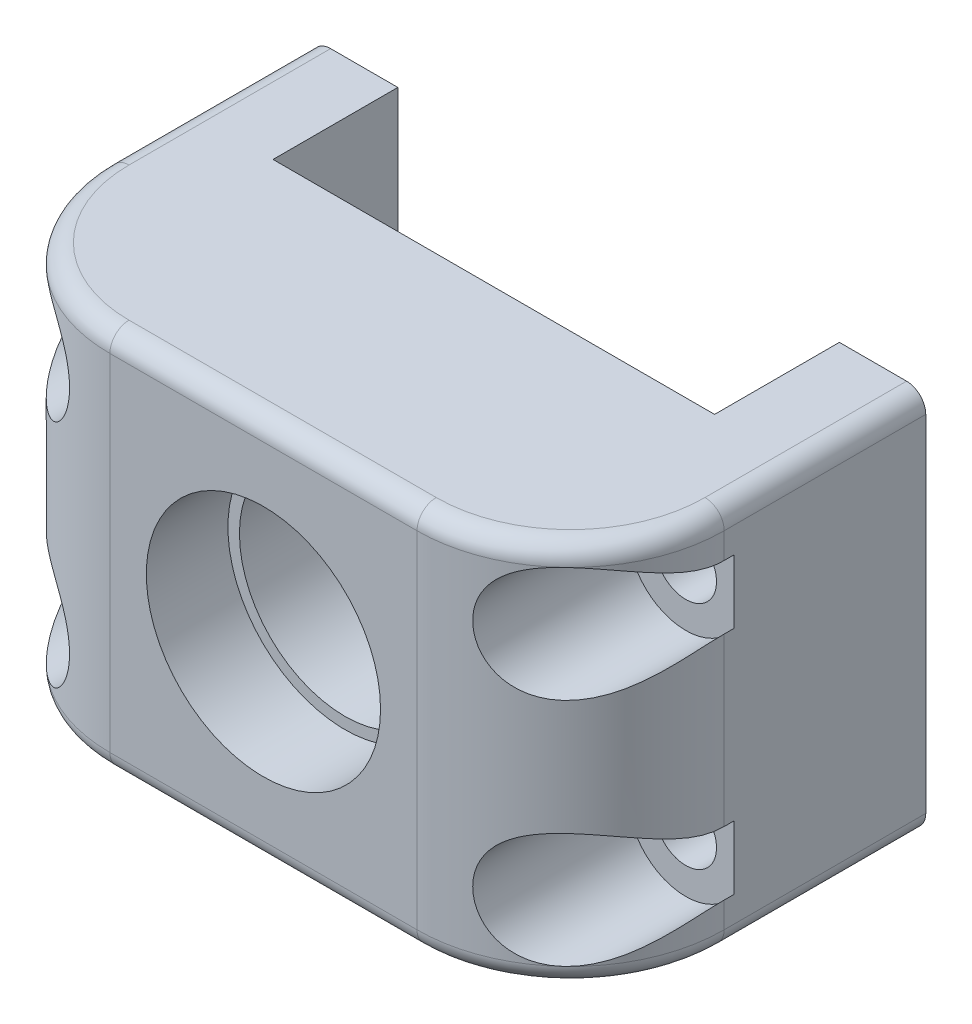
SolidWorks part; units mm, degrees
ref_plane "Front Plane" through (0, 0, 0) normal (0, 0, 1) x (1, 0, 0)
ref_plane "Top Plane" through (0, 0, 0) normal (0, 1, 0) x (1, 0, 0)
ref_plane "Right Plane" through (0, 0, 0) normal (1, 0, 0) x (0, 0, -1)
sketch "Sketch3" plane through (0, 0, 0) normal (0, 0, 1) x (1, 0, 0)
  line L1 (-16, -10) -> (16, -10)
  line L2 (-16, -10) -> (-16, 10)
  line L3 (-16, 10) -> (16, 10)
  line L4 (16, -10) -> (16, 10)
  line L5 (-16, -10) -> (16, 10) construction
  line L6 (-16, 10) -> (16, -10) construction
  circle A1 centre (-13.5, 6) radius 1.6
  circle A2 centre (-13.5, -6) radius 1.6
  circle A3 centre (13.5, -6) radius 1.6
  circle A4 centre (13.5, 6) radius 1.6
  point P19 (0, 0)
  dimension "D1" = 3.2
  dimension "D2" = 32
  dimension "D3" = 20
  dimension "D4" = 27
  dimension "D5" = 12
  dimension "D6" = 13.5
  dimension "D7" = 6
extrude "Boss-Extrude1" add sketch "Sketch3" along normal blind 18.5
sketch "Sketch5" plane through (0, 10, 0) normal (0, 1, 0) x (1, 0, 0)
  line L0 (16, 0) -> (-16, 0) construction
  line L1 (-11.5, 0) -> (11.5, 0)
  line L2 (-11.5, 0) -> (-11.5, -6.5)
  line L3 (-11.5, -6.5) -> (11.5, -6.5)
  line L4 (11.5, 0) -> (11.5, -6.5)
  line L6 (16, -18.5) -> (-16, -18.5) construction
  point P6 (0, 0)
  dimension "D1" = 23
  dimension "D2" = 12
extrude "Cut-Extrude1" cut sketch "Sketch5" against normal up to next
fillet "Fillet2" radius 8 2 edges at (16, 0, 18.5) (-16, 0, 18.5)
fillet "Fillet1" radius 1 10 edges at (16, -10, 5.25) (-16, -10, 5.25) (16, 10, 5.25) (-16, 10, 5.25) (13.6569, -10, 16.1569) (0, -10, 18.5) (-13.6569, -10, 16.1569) (13.6569, 10, 16.1569) (0, 10, 18.5) (-13.6569, 10, 16.1569)
sketch "Sketch9" plane through (0, 0, 0) normal (0, 0, -1) x (-1, 0, 0)
  circle A0 centre (-13.5, 6) radius 3
  circle A1 centre (-13.5, -6) radius 3
  circle A2 centre (13.5, -6) radius 3
  circle A3 centre (13.5, 6) radius 3
  dimension "D1" = 6
extrude "Cut-Extrude5" cut sketch "Sketch9" against normal up to next from offset 10 offset against normal yes
sketch "Sketch10" plane through (0, 0, 18.5) normal (0, 0, 1) x (1, 0, 0)
  circle A0 centre (0, 0) radius 6.1
  dimension "D1" = 12.2
extrude "Cut-Extrude6" cut sketch "Sketch10" against normal blind 4.25
sketch "Sketch12" plane through (0, 0, 6.5) normal (0, 0, -1) x (-1, 0, 0)
  circle A0 centre (0, 0) radius 6.1
  dimension "D1" = 12.2
extrude "Cut-Extrude7" cut sketch "Sketch12" against normal blind 3.5
sketch "Sketch13" plane through (0, 0, 10) normal (0, 0, -1) x (-1, 0, 0)
  circle A0 centre (0, 0) radius 5.5
  dimension "D1" = 11
extrude "Cut-Extrude8" cut sketch "Sketch13" against normal up to next
equation "\"D6@Sketch3\"=\"D4@Sketch3\"/2"
equation "\"D7@Sketch3\"=\"D5@Sketch3\"/2"
